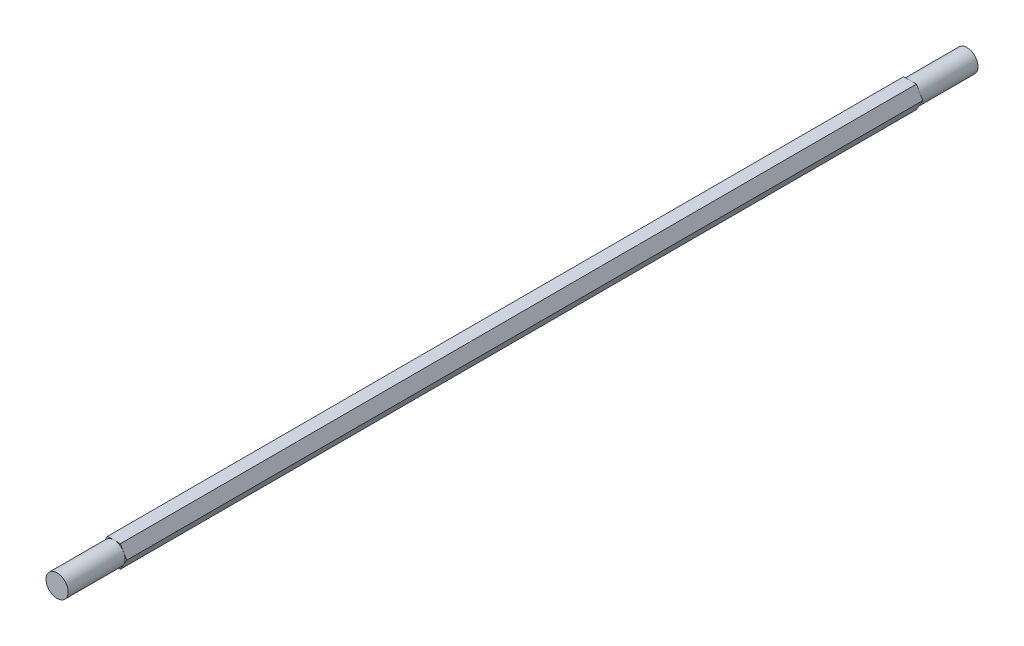
SolidWorks part; units mm, degrees
material "AISI 18-8"
ref_plane "Front Plane" through (0, 0, 0) normal (0, 0, 1) x (1, 0, 0)
ref_plane "Top Plane" through (0, 0, 0) normal (0, 1, 0) x (1, 0, 0)
ref_plane "Right Plane" through (0, 0, 0) normal (1, 0, 0) x (0, 0, -1)
sketch "Sketch1" plane through (0, 0, 0) normal (0, 0, 1) x (1, 0, 0)
  circle A0 centre (0, 0) radius 4.953
  dimension "D1" = 9.906
extrude "Boss-Extrude1" add sketch "Sketch1" along normal blind 203.2 and the other way blind 203.2
sketch "Sketch2" plane through (0, 0, 0) normal (0, 0, 1) x (1, 0, 0)
  line L1 (5.7192, 0) -> (2.8596, 4.953)
  line L2 (2.8596, 4.953) -> (-2.8596, 4.953)
  line L3 (-2.8596, 4.953) -> (-5.7192, 0)
  line L4 (-5.7192, 0) -> (-2.8596, -4.953)
  line L5 (-2.8596, -4.953) -> (2.8596, -4.953)
  line L6 (2.8596, -4.953) -> (5.7192, 0)
  circle A0 centre (0, 0) radius 4.953 construction
  circle A1 centre (0, 0) radius 4.953 construction
  point P11 (0, 0)
extrude "Boss-Extrude2" add sketch "Sketch2" along normal blind 177.8 and the other way blind 177.8
